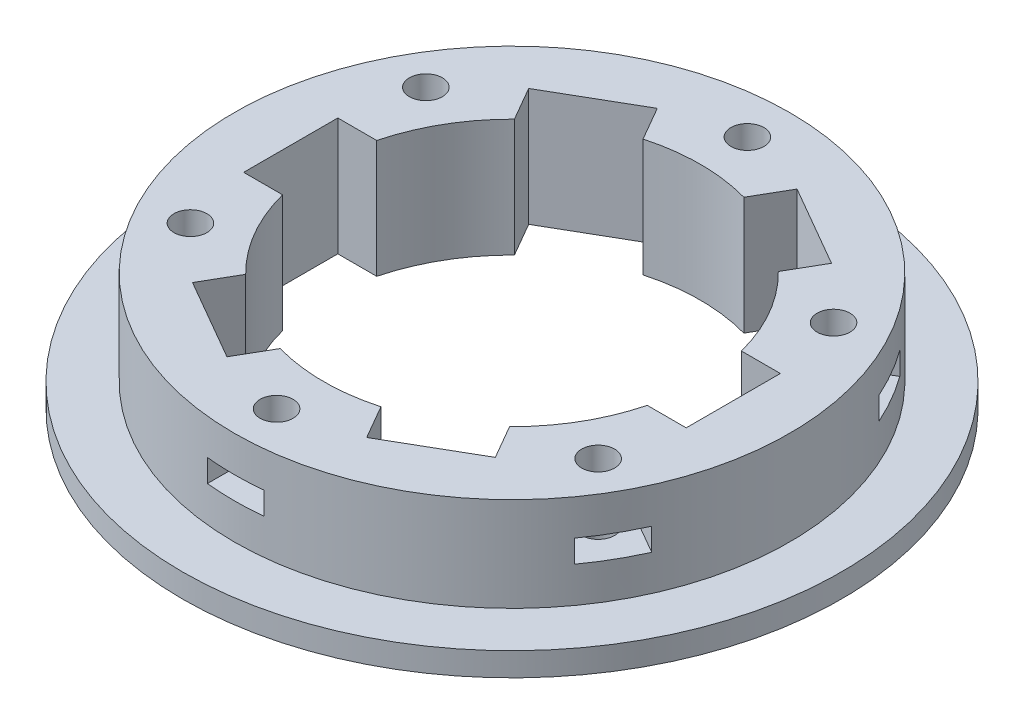
SolidWorks part; units mm, degrees
ref_plane "Front Plane" through (0, 0, 0) normal (0, 0, 1) x (1, 0, 0)
ref_plane "Top Plane" through (0, 0, 0) normal (0, 1, 0) x (1, 0, 0)
ref_plane "Right Plane" through (0, 0, 0) normal (1, 0, 0) x (0, 0, -1)
sketch "Sketch1" plane through (0, 0, 0) normal (0, 1, 0) x (1, 0, 0)
  circle A0 centre (0, 0) radius 35
  circle A1 centre (0, 0) radius 30 construction
  circle A2 centre (0, 0) radius 20
  dimension "D1" = 70
  dimension "D2" = 60
  dimension "D3" = 40
extrude "Boss-Extrude1" add sketch "Sketch1" along normal blind 2.5
sketch "Sketch2" plane through (0, 2.5, 0) normal (0, 1, 0) x (1, 0, 0)
  circle A0 centre (0, 0) radius 29.5
  circle A1 centre (0, 0) radius 20
  dimension "D1" = 59
  dimension "D2" = 40
extrude "Boss-Extrude2" add sketch "Sketch2" along normal blind 10
sketch "Sketch3" plane through (0, 12.5, 0) normal (0, 1, 0) x (1, 0, 0)
  line L0 (0, 0) -> (-35, 0) construction
  line L1 (0, 0) -> (0, -35) construction
  line L2 (-19.3649, 5) -> (-23.5, 5)
  line L3 (23.5, -5) -> (19.3649, -5) construction
  line L4 (23.5, -5) -> (23.5, 5) construction
  line L5 (23.5, 5) -> (19.3649, 5) construction
  line L6 (-23.5, -5) -> (-23.5, 5)
  line L7 (23.5, -5) -> (-23.5, 5) construction
  line L8 (23.5, 5) -> (-23.5, -5) construction
  line L9 (-19.3649, -5) -> (-23.5, -5)
  line L10 (-5.3523, 19.2705) -> (-7.4199, 22.8516)
  line L11 (-16.0801, 17.8516) -> (-7.4199, 22.8516)
  line L12 (-14.0126, 14.2705) -> (-16.0801, 17.8516)
  line L13 (14.0126, 14.2705) -> (16.0801, 17.8516)
  line L14 (7.4199, 22.8516) -> (16.0801, 17.8516)
  line L15 (5.3523, 19.2705) -> (7.4199, 22.8516)
  line L16 (19.3649, -5) -> (23.5, -5)
  line L17 (23.5, 5) -> (23.5, -5)
  line L18 (19.3649, 5) -> (23.5, 5)
  line L19 (5.3523, -19.2705) -> (7.4199, -22.8516)
  line L20 (16.0801, -17.8516) -> (7.4199, -22.8516)
  line L21 (14.0126, -14.2705) -> (16.0801, -17.8516)
  line L22 (-14.0126, -14.2705) -> (-16.0801, -17.8516)
  line L23 (-7.4199, -22.8516) -> (-16.0801, -17.8516)
  line L24 (-5.3523, -19.2705) -> (-7.4199, -22.8516)
  circle A0 centre (0, 0) radius 35 construction
  arc A1 (19.3649, -5) -> (19.3649, 5) centre (0, 0) ccw construction
  arc A2 (-19.3649, 5) -> (-19.3649, -5) centre (0, 0) ccw
  arc A3 (-5.3523, 19.2705) -> (-14.0126, 14.2705) centre (0, 0) ccw
  arc A4 (14.0126, 14.2705) -> (5.3523, 19.2705) centre (0, 0) ccw
  arc A5 (19.3649, -5) -> (19.3649, 5) centre (0, 0) ccw
  arc A6 (5.3523, -19.2705) -> (14.0126, -14.2705) centre (0, 0) ccw
  arc A7 (-14.0126, -14.2705) -> (-5.3523, -19.2705) centre (0, 0) ccw
  point P37 (0, 0)
  dimension "D1" = 47
  dimension "D3" = 40
  dimension "D2" = 10
  dimension "D4" = 6
sketch "Sketch4" plane through (0, 12.5, 0) normal (0, 1, 0) x (1, 0, 0)
  line L0 (0, 0) -> (-45.5771, 0) construction
  line L1 (0, 0) -> (-43.3013, -25) construction
  circle A0 centre (0, 0) radius 25 construction
  circle A1 centre (-21.6506, -12.5) radius 1.75
  circle A2 centre (-21.6506, 12.5) radius 1.75
  circle A3 centre (0, 25) radius 1.75
  circle A4 centre (21.6506, 12.5) radius 1.75
  circle A5 centre (21.6506, -12.5) radius 1.75
  circle A6 centre (0, -25) radius 1.75
  point P16 (0, 0)
  point P20 (0, 0)
  dimension "D1" = 50
  dimension "D2" = 30
  dimension "D3" = 3.5
  dimension "D4" = 6
extrude "Cut-Extrude2" cut sketch "Sketch4" against normal through all
extrude "Cut-Extrude1" cut sketch "Sketch3" against normal through all
ref_plane "Plane2" through (0, 7.5, 0) normal (0, 1, 0) x (1, 0, 0)
sketch "Sketch7" plane through (0, 7.5, 0) normal (0, 1, 0) x (1, 0, 0)
  line L0 (0, 0) -> (0, -35) construction
  line L1 (-18.6506, -10.7679) -> (-21.6506, -9.0359)
  line L2 (0, -21.5359) -> (-3, -23.2679)
  line L3 (-3, -23.2679) -> (-3, -29.3471)
  line L4 (-21.6506, -9.0359) -> (-26.9153, -12.0755)
  line L5 (-23.9153, -17.2716) -> (-18.6506, -14.2321)
  line L6 (3, -29.3471) -> (3, -23.2679)
  line L7 (3, -23.2679) -> (0, -21.5359)
  line L8 (0, -28.4641) -> (1.5, -27.5981) [skipped]
  line L9 (-3, -26.7321) -> (-1.5, -27.5981) [skipped]
  line L10 (-18.6506, -14.2321) -> (-18.6506, -10.7679)
  line L11 (-18.6506, 10.7679) -> (-18.6506, 14.2321)
  line L12 (-18.6506, 14.2321) -> (-23.9153, 17.2716)
  line L13 (-26.9153, 12.0755) -> (-21.6506, 9.0359)
  line L14 (-21.6506, 9.0359) -> (-18.6506, 10.7679)
  line L15 (0, 21.5359) -> (3, 23.2679)
  line L16 (3, 23.2679) -> (3, 29.3471)
  line L17 (-3, 29.3471) -> (-3, 23.2679)
  line L18 (-3, 23.2679) -> (0, 21.5359)
  line L19 (18.6506, 10.7679) -> (21.6506, 9.0359)
  line L20 (21.6506, 9.0359) -> (26.9153, 12.0755)
  line L21 (23.9153, 17.2716) -> (18.6506, 14.2321)
  line L22 (18.6506, 14.2321) -> (18.6506, 10.7679)
  line L23 (18.6506, -10.7679) -> (18.6506, -14.2321)
  line L24 (18.6506, -14.2321) -> (23.9153, -17.2716)
  line L25 (26.9153, -12.0755) -> (21.6506, -9.0359)
  line L26 (21.6506, -9.0359) -> (18.6506, -10.7679)
  circle A0 centre (0, 0) radius 35 construction
  circle A1 centre (0, -25) radius 3 construction
  arc A2 (-3, -29.3471) -> (3, -29.3471) centre (0, 0) ccw
  arc A3 (-26.9153, -12.0755) -> (-23.9153, -17.2716) centre (0, 0) ccw
  circle A4 centre (-21.6506, -12.5) radius 3 construction
  arc A5 (-23.9153, 17.2716) -> (-26.9153, 12.0755) centre (0, 0) ccw
  circle A6 centre (-21.6506, 12.5) radius 3 construction
  arc A7 (3, 29.3471) -> (-3, 29.3471) centre (0, 0) ccw
  circle A8 centre (0, 25) radius 3 construction
  arc A9 (26.9153, 12.0755) -> (23.9153, 17.2716) centre (0, 0) ccw
  circle A10 centre (21.6506, 12.5) radius 3 construction
  arc A11 (23.9153, -17.2716) -> (26.9153, -12.0755) centre (0, 0) ccw
  circle A12 centre (21.6506, -12.5) radius 3 construction
  point P54 (0, 0)
  dimension "D1" = 6
  dimension "D2" = 59
  dimension "D3" = 6
extrude "Cut-Extrude3" cut sketch "Sketch7" against normal blind 1.2 and the other way blind 1.2
